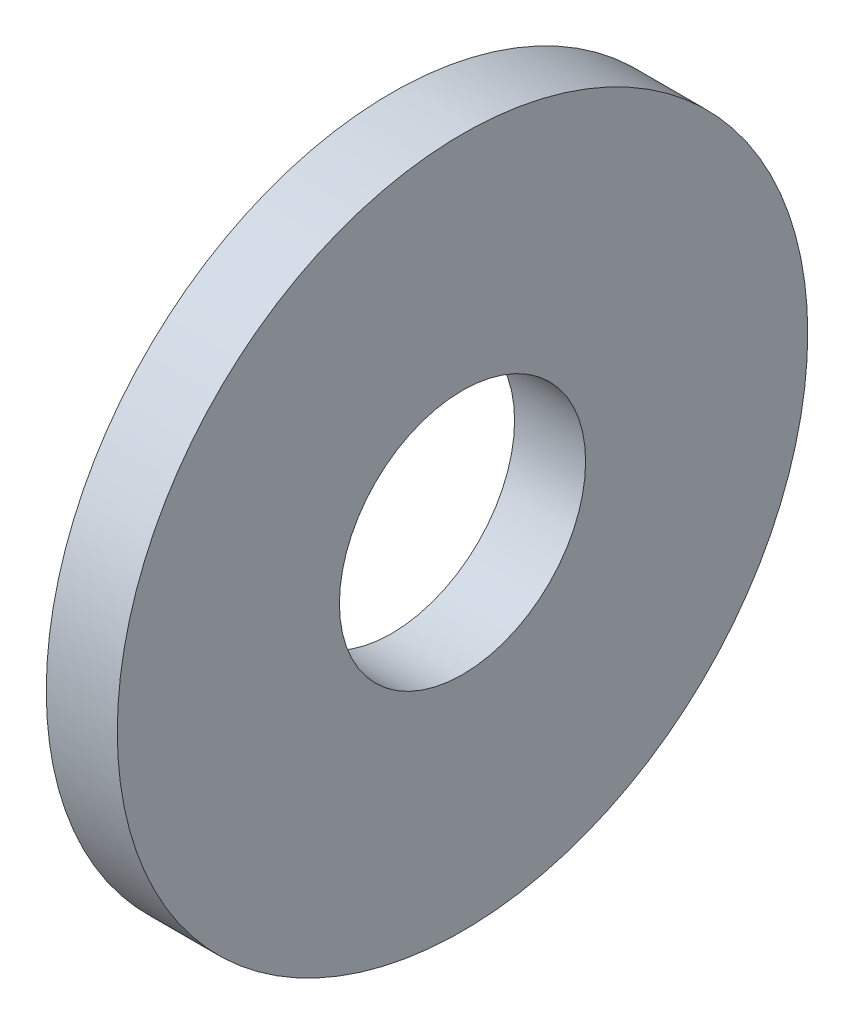
SolidWorks part; units mm, degrees
material "Nylon 6/10"
ref_plane "Front Plane" through (0, 0, 0) normal (0, 0, 1) x (1, 0, 0)
ref_plane "Top Plane" through (0, 0, 0) normal (0, 1, 0) x (1, 0, 0)
ref_plane "Right Plane" through (0, 0, 0) normal (1, 0, 0) x (0, 0, -1)
ref_axis "Centre Axis" through (-0.0571, 0, 0) along (1, 0, 0)
sketch "Sketch1" plane through (0, 0, 0) normal (1, 0, 0) x (0, 0, -1)
  circle A0 centre (0, 0) radius 5.5562
  circle A1 centre (0, 0) radius 1.9812
  dimension "OD" = 11.1125
  dimension "ID" = 3.9624
extrude "Boss-Extrude1" add sketch "Sketch1" along normal blind 1.143
